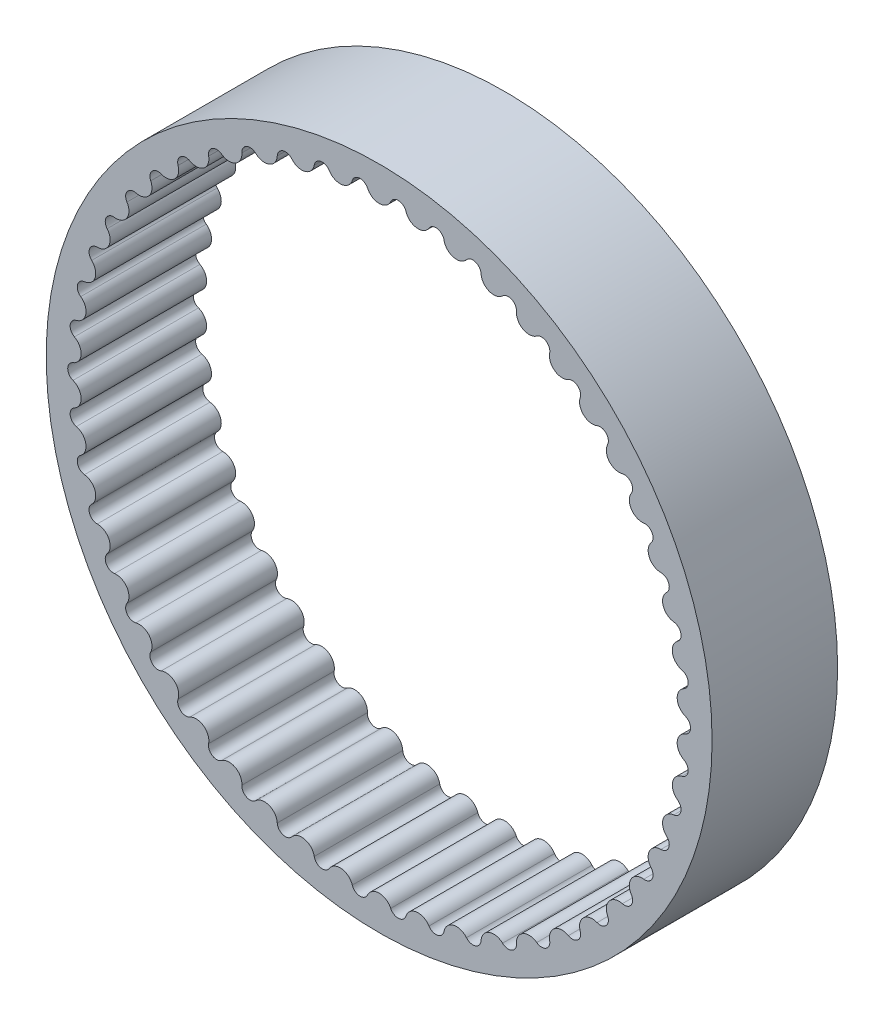
SolidWorks part; units mm, degrees
ref_plane "Front Plane" through (0, 0, 0) normal (0, 0, 1) x (1, 0, 0)
ref_plane "Top Plane" through (0, 0, 0) normal (0, 1, 0) x (1, 0, 0)
ref_plane "Right Plane" through (0, 0, 0) normal (1, 0, 0) x (0, 0, -1)
sketch "Sketch1" plane through (0, 0, 0) normal (0, 0, 1) x (1, 0, 0)
  line L0 (0, 0) -> (0, 14.8855) construction
  line L1 (0, 0) -> (1.8656, 14.7681) construction
  line L2 (0, 0) -> (3.7019, 14.4179) construction
  line L3 (-1.8656, 14.7681) -> (0, 0) construction
  circle A0 centre (0, 0) radius 15.9155
  circle A1 centre (0, 0) radius 14.2755
  circle A2 centre (0, 0) radius 14.8855 construction
  circle A10 centre (0, 14.8855) radius 0.61
  circle A101 centre (1.8656, 14.7681) radius 0.61
  circle A102 centre (0.91, 14.464) radius 0.3929
  circle A103 centre (-0.91, 14.464) radius 0.3929
  circle A104 centre (-1.8656, 14.7681) radius 0.61
  point P16 (-1.7892, 14.1629)
  point P17 (0, 14.2755)
  point P77 (0, 0)
  dimension "OD" = 31.831
  dimension "Tooth Diameter" = 1.22
  dimension "Belt Thickness" = 1.64
  dimension "Angle" = 7.2
  dimension "D3" = 7.2
sketch "Sketch2" plane through (0, 0, 0) normal (0, 0, 1) x (1, 0, 0)
  circle A0 centre (0, 0) radius 14.2755 construction
  circle A1 centre (0, 0) radius 15.9155 construction
  circle A2 centre (0, 0) radius 14.2755
  circle A3 centre (0, 0) radius 15.9155
extrude "Boss-Extrude1" add sketch "Sketch2" along normal mid plane 6
sketch "Sketch3" plane through (0, 0, 0) normal (0, 0, 1) x (1, 0, 0)
  circle A0 centre (0, 0) radius 14.2755 construction
  circle A1 centre (1.8656, 14.7681) radius 0.61 construction
  circle A2 centre (0.91, 14.464) radius 0.3929 construction
  circle A3 centre (0, 14.8855) radius 0.61 construction
  arc A4 (1.7892, 14.1629) -> (0, 14.2755) centre (0, 0) ccw
  arc A5 (1.2844, 14.5832) -> (1.7892, 14.1629) centre (1.8656, 14.7681) ccw
  arc A6 (1.2844, 14.5832) -> (0.5535, 14.6292) centre (0.91, 14.464) ccw
  arc A7 (0, 14.2755) -> (0.5535, 14.6292) centre (0, 14.8855) ccw
extrude "Cut-Extrude1" cut sketch "Sketch3" against normal through all both and the other way through all
pattern_circular "CirPattern3" count 50 over 360 about axis through (0, 0, 3) along (0, 0, -1) of "Cut-Extrude1"
ref_axis "Center Axis 1" through (0, 0, 3) along (0, 0, -1)
equation "\"D3@Sketch1\" = \"Angle@Sketch1\""
